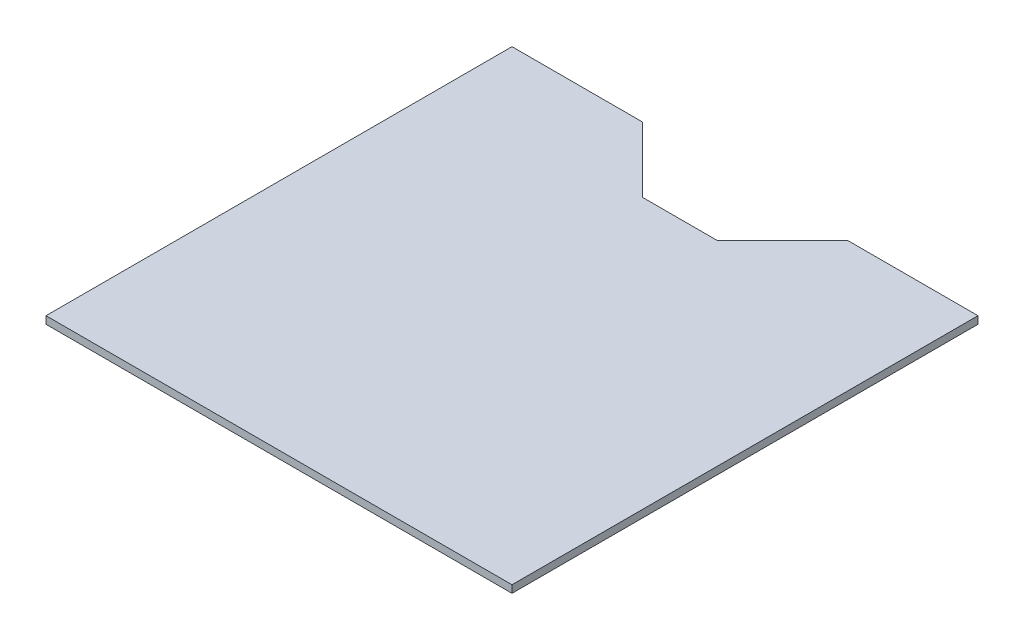
SolidWorks part; units mm, degrees
material "1060 合金"
ref_plane "前视基准面" through (0, 0, 0) normal (0, 0, 1) x (1, 0, 0)
ref_plane "上视基准面" through (0, 0, 0) normal (0, 1, 0) x (1, 0, 0)
ref_plane "右视基准面" through (0, 0, 0) normal (1, 0, 0) x (0, 0, -1)
ref_axis "中轴" through (0, -11.5924, 0) along (0, 1, 0)
sketch "草图1" plane through (0, 0, 0) normal (0, 1, 0) x (1, 0, 0)
  line L1 (-250, -250) -> (250, -250)
  line L2 (-250, -250) -> (-250, 250)
  line L3 (-250, 250) -> (250, 250)
  line L4 (250, -250) -> (250, 250)
  line L5 (-250, -250) -> (250, 250) construction
  line L6 (-250, 250) -> (250, -250) construction
  point P0 (0, 0)
  dimension "D1" = 500
  dimension "D2" = 500
extrude "凸台-拉伸1" add sketch "草图1" along normal mid plane 8
sketch "草图3" plane through (0, 4, 0) normal (0, 1, 0) x (1, 0, 0)
  line L0 (250, 250) -> (-250, 250) construction
  line L1 (250, 250) -> (-250, 250) construction
  line L2 (0, 0) -> (0, 283.6146) construction
  line L3 (110, 250) -> (40, 180)
  line L4 (40, 180) -> (-40, 180)
  line L5 (-110, 250) -> (-40, 180)
  point P10 (0, 180)
  dimension "D1" = 45
  dimension "D2" = 80
  dimension "D3" = 220
extrude "切除-拉伸1" cut sketch "草图3" against normal through all and the other way through all
sketch3d "球剖面"
  circle A0 centre (0, -4, -284) radius 62.6099
  circle A1 centre (0, -4, -284) radius 62.6099 construction
  point P2 (0, -66.6099, -284)
  point P4 (0, -66.6099, -284)
  dimension "d" = 10
